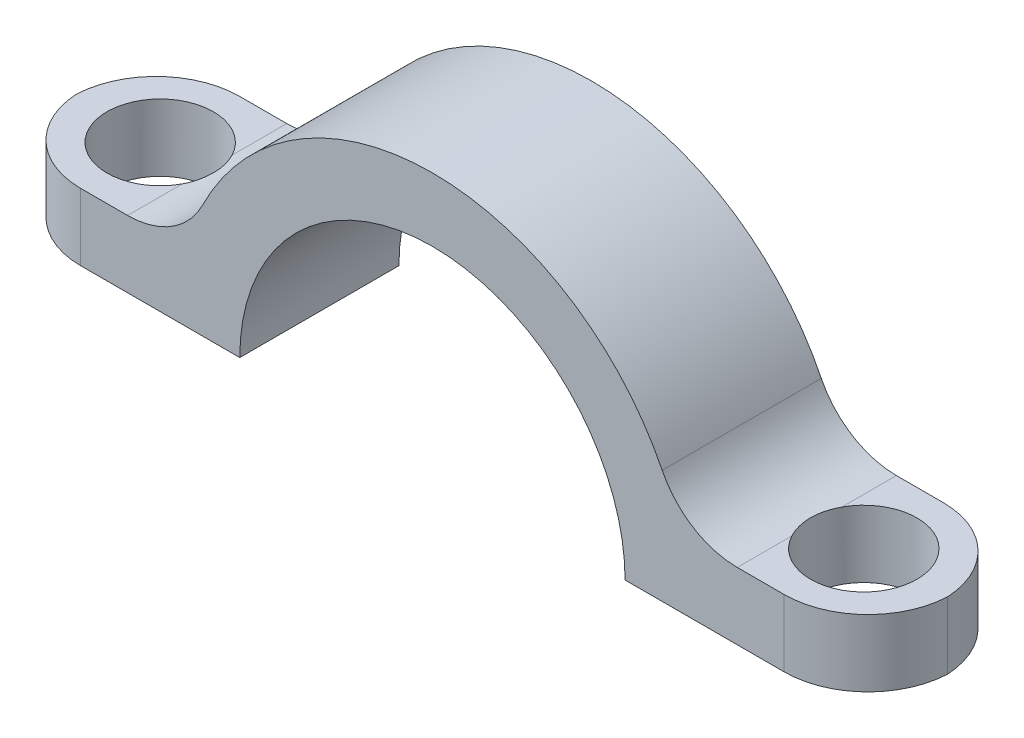
SolidWorks part; units mm, degrees
ref_plane "Front Plane" through (0, 0, 0) normal (0, 0, 1) x (1, 0, 0)
ref_plane "Top Plane" through (0, 0, 0) normal (0, 1, 0) x (1, 0, 0)
ref_plane "Right Plane" through (0, 0, 0) normal (1, 0, 0) x (0, 0, -1)
sketch "Sketch1" plane through (0, 0, 0) normal (0, 0, 1) x (1, 0, 0)
  line L0 (11.5, 0) -> (26, 0)
  line L1 (-11.5, 0) -> (-26, 0)
  line L2 (-26, 0) -> (-26, 4)
  line L3 (26, 0) -> (26, 4)
  line L4 (-26, 4) -> (-14.7679, 4)
  line L5 (26, 4) -> (14.7679, 4)
  arc A0 (11.5, 0) -> (-11.5, 0) centre (0, 0) ccw
  arc A1 (14.7679, 4) -> (-14.7679, 4) centre (0, 0) ccw
  dimension "D1" = 23
  dimension "D5" = 30.6
  dimension "D2" = 52
  dimension "D3" = 4
  dimension "D4" = 4
extrude "Boss-Extrude1" add sketch "Sketch1" along normal blind 9.5
fillet "Fillet5" radius 5 2 edges at (14.7679, 4, 4.75) (-14.7679, 4, 4.75)
sketch "Sketch2" plane through (0, 4, 0) normal (0, 1, 0) x (1, 0, 0)
  line L1 (-26, -9.5) -> (-26, 0) construction
  circle A0 centre (-21, -4.75) radius 3.175
  circle A1 centre (21, -4.75) radius 3.175
  point P7 (-26, -4.75)
  dimension "D1" = 6.35
  dimension "D2" = 6.35
  dimension "D3" = 42
  dimension "D4" = 5
extrude "Cut-Extrude1" cut sketch "Sketch2" against normal through all both and the other way through all contours A0 | A1
fillet "Fillet1" radius 5 4 edges at (-26, 2, 0) (26, 2, 0) (26, 2, 9.5) (-26, 2, 9.5)
